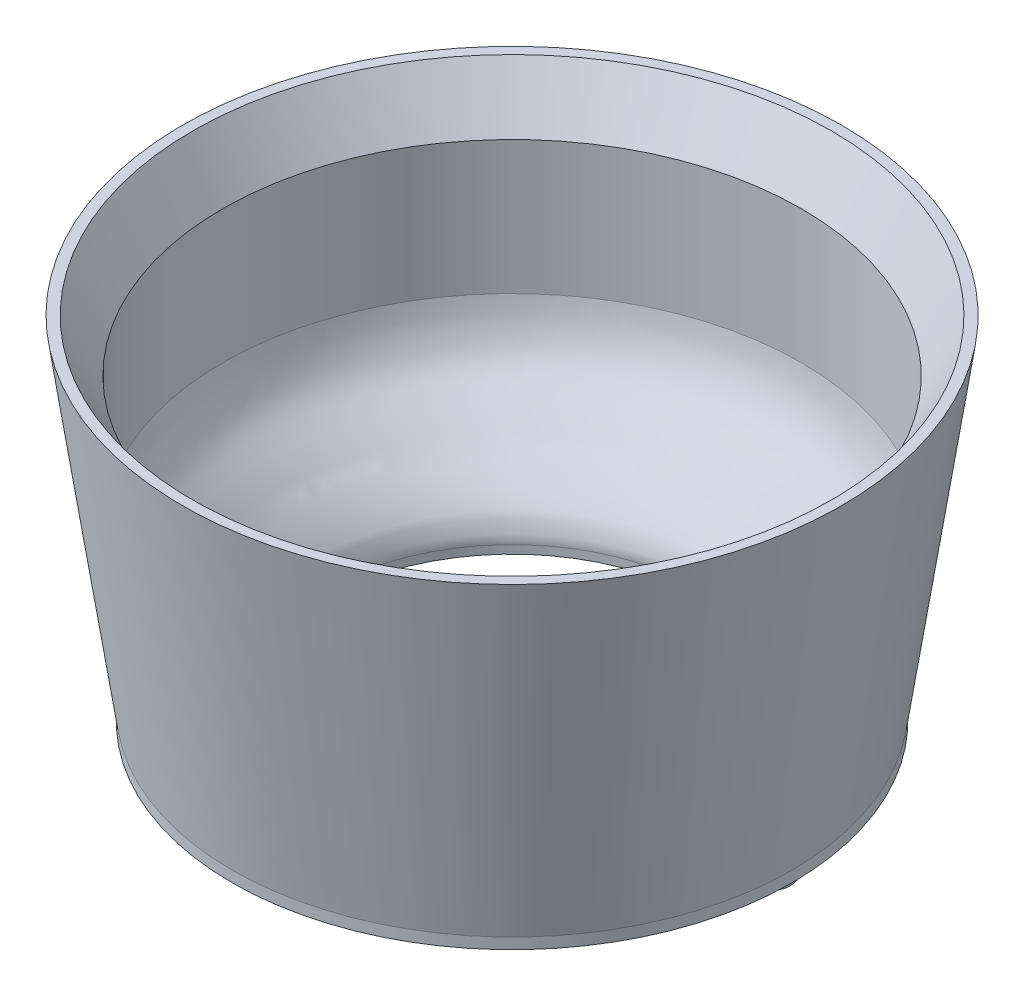
SolidWorks part; units mm, degrees
material "ABS PC"
ref_plane "Front Plane" through (0, 0, 0) normal (0, 0, 1) x (1, 0, 0)
ref_plane "Top Plane" through (0, 0, 0) normal (0, 1, 0) x (1, 0, 0)
ref_plane "Right Plane" through (0, 0, 0) normal (1, 0, 0) x (0, 0, -1)
sketch "Sketch1" plane through (0, 0, 0) normal (1, 0, 0) x (0, 0, -1)
  line L0 (26.0878, 274.978) -> (26.0878, 232.1195)
  line L2 (40.135, 299.274) -> (-40.135, 299.274) construction
  line L5 (0, 324) -> (3.2968, 324)
  line L8 (0, 324) -> (0, 0) construction
  line L9 (26.0878, 262.3641) -> (26.0878, 259.4973) construction
  line L12 (40.135, 302.9291) -> (40.135, 295.6188)
  line L16 (0, 0) -> (51.9362, 327.9125) construction
  line L17 (0, 324) -> (0, 332) construction
  line L18 (26.0878, 274.978) -> (26.0878, 268.978) construction
  line L19 (26.0878, 268.978) -> (26.0878, 248.978) construction
  line L20 (26.0878, 268.978) -> (42.6019, 268.978) construction
  line L21 (26.0878, 274.978) -> (43.5522, 274.978) construction
  line L22 (26.0878, 248.978) -> (39.4342, 248.978) construction
  line L23 (0, 0) -> (-51.9362, 327.9125) construction
  line L24 (-47.4003, 299.274) -> (-47.4003, 268.978) construction
  line L25 (-47.4003, 268.978) -> (-42.6019, 268.978) construction
  line L26 (0, 332) -> (0, 76.96) construction
  line L27 (0, 76.96) -> (400, 76.96) construction
  line L28 (0, 76.96) -> (-400, 76.96) construction
  line L29 (-200, 76.96) -> (-200, 183.96) construction
  line L30 (200, 76.96) -> (200, 183.96) construction
  line L31 (-200, 183.96) -> (-200, 182.57) construction
  line L32 (-200, 182.57) -> (400, 182.57) construction
  line L33 (-200, 182.57) -> (-400, 182.57) construction
  line L38 (0, 186.1152) -> (0, 324)
  line L39 (26.0878, 232.1195) -> (26.0878, 182.57) construction
  line L41 (21.6442, 226.0993) -> (26.0878, 226.0993)
  line L42 (26.0878, 226.0993) -> (26.0878, 186.1152)
  line L43 (26.0878, 186.1152) -> (0, 186.1152)
  line L44 (0, 0) -> (575.122, 0) construction
  arc A0 (-298.7691, 144.7791) -> (305.6579, 129.6043) centre (0, 0) cw construction
  spline S0 degree 3 poles (21.6442, 226.0993) (21.9584, 226.1509) (22.4049, 226.153) (22.896, 226.3321) (23.44, 226.7494) (24.2443, 227.2014) (25.0066, 227.9724) (25.5796, 228.9522) (25.8622, 230.393) (26.0228, 231.4436) (26.0878, 232.1195) knots 0 0 0 0 0.091924 0.112491 0.205673 0.333714 0.459267 0.602423 0.748839 1 1 1 1
  spline S1 degree 3 poles (3.2968, 324) (4.1972, 323.8396) (5.699, 323.816) (7.6935, 323.4297) (9.2722, 323.1563) (10.7507, 322.8538) (12.1816, 322.5577) (13.6372, 322.313) (14.8643, 321.9117) (15.9115, 321.5662) (16.81, 321.2491) (17.7339, 321.0149) (18.8379, 320.6416) (19.931, 320.1935) (21.0686, 319.6948) (22.141, 319.2627) (23.2156, 318.6856) (24.4371, 318.1163) (25.6762, 317.3518) (27.1066, 316.7518) (28.4318, 315.7832) (29.7322, 314.8939) (31.058, 313.93) (32.1959, 312.8581) (33.3378, 311.8503) (34.4539, 310.9646) (35.3895, 309.8867) (36.5078, 309.0949) (37.2942, 308.0208) (38.1233, 307.1238) (38.9048, 306.0961) (39.4724, 304.6349) (40.2774, 303.734) (40.135, 302.9291) knots 0 0 0 0 0.061585 0.100795 0.136831 0.1697 0.202569 0.235438 0.269088 0.289473 0.309858 0.333319 0.353706 0.388423 0.412965 0.437514 0.46634 0.495168 0.528354 0.564387 0.59925 0.638593 0.670824 0.709635 0.743897 0.773612 0.805519 0.839783 0.864953 0.89467 0.922395 0.951224 1 1 1 1
  spline S2 degree 3 poles (40.135, 295.6188) (39.9636, 294.7131) (39.7869, 293.3689) (39.1095, 291.6901) (38.6019, 290.4599) (37.8418, 289.2392) (36.9195, 288.2279) (35.9232, 287.2651) (34.974, 286.2515) (33.8311, 285.3463) (32.8233, 284.2966) (31.8701, 283.2868) (30.7668, 282.4387) (29.8742, 281.4644) (28.8604, 280.5152) (28.0567, 279.5119) (27.1438, 278.5569) (26.4968, 277.0287) (26.0081, 275.8567) (26.0878, 274.978) knots 0 0 0 0 0.108356 0.15601 0.210945 0.263562 0.322855 0.370186 0.4254 0.484692 0.539909 0.595126 0.646549 0.701764 0.749093 0.808384 0.85195 0.901837 1 1 1 1
  point P10 (0, 299.274)
  point P63 (0, 299.274)
  dimension "D3" = 9
  dimension "D1" = 40.135
  dimension "D2" = 324
  dimension "D4" = 8
  dimension "D5" = 3.2968
  dimension "D6" = 4.4435
  dimension "D7" = 6.0202
  dimension "D8" = 7.7403
  dimension "D9" = 6
  dimension "D10" = 20
  dimension "D11" = 9.317
  dimension "D12" = 10.7504
  dimension "D13" = 255.04
  dimension "D14" = 107
  dimension "D15" = 107
  dimension "D16" = 332
  dimension "D17" = 105.61
  dimension "D18" = 105.61
  dimension "D19" = 12.1838
  dimension "D20" = 13.6172
  dimension "D21" = 15.0506
  dimension "D22" = 15.9106
  dimension "D23" = 16.7707
  dimension "D24" = 17.7739
  dimension "D25" = 18.6341
  dimension "D26" = 20.0676
  dimension "D27" = 21.0708
  dimension "D28" = 22.0743
  dimension "D29" = 23.2209
  dimension "D30" = 24.3677
  dimension "D31" = 25.6578
  dimension "D32" = 27.0911
  dimension "D33" = 28.3811
  dimension "D34" = 29.8146
  dimension "D35" = 30.9613
  dimension "D36" = 32.2513
  dimension "D37" = 33.3981
  dimension "D38" = 34.4014
  dimension "D39" = 35.4048
  dimension "D40" = 36.5516
  dimension "D41" = 37.2681
  dimension "D42" = 38.1282
  dimension "D43" = 38.8449
  dimension "D44" = 39.4183
  dimension "D45" = 39.9917
  dimension "D46" = 323.8567
  dimension "D47" = 323.7133
  dimension "D48" = 323.4267
  dimension "D49" = 323.1399
  dimension "D50" = 322.8533
  dimension "D51" = 322.5666
  dimension "D52" = 322.2799
  dimension "D53" = 321.8499
  dimension "D54" = 321.5632
  dimension "D55" = 321.2765
  dimension "D56" = 320.9899
  dimension "D57" = 320.7031
  dimension "D58" = 320.1297
  dimension "D59" = 319.6998
  dimension "D60" = 319.2698
  dimension "D61" = 318.6965
  dimension "D62" = 318.1231
  dimension "D63" = 317.4064
  dimension "D64" = 316.6897
  dimension "D65" = 315.8296
  dimension "D66" = 314.8263
  dimension "D67" = 313.9663
  dimension "D68" = 312.8195
  dimension "D69" = 311.8162
  dimension "D70" = 310.9562
  dimension "D71" = 309.9528
  dimension "D72" = 308.9493
  dimension "D73" = 308.0893
  dimension "D74" = 307.086
  dimension "D75" = 306.0826
  dimension "D76" = 304.9359
  dimension "D77" = 303.9325
  dimension "D78" = 302.9291
sketch "Sketch2" plane through (0, 0, 0) normal (1, 0, 0) x (0, 0, -1)
  line L0 (0, 324) -> (3.2968, 324) construction
  line L1 (26.5078, 274.997) -> (26.5078, 273.8486)
  line L2 (40.5477, 295.5407) -> (40.5477, 314.2386)
  line L3 (40.135, 295.6188) -> (40.135, 302.9302) construction
  line L4 (40.135, 295.6188) -> (26.0878, 274.978) construction
  line L5 (0, 324.42) -> (3.4084, 324.42) construction
  line L6 (3.2968, 324) -> (40.135, 302.9302) construction
  line L7 (3.4084, 324.42) -> (40.555, 303.1738) construction
  line L8 (26.0878, 274.978) -> (26.0878, 232.1195) construction
  line L9 (40.555, 295.4895) -> (26.435, 274.7417) construction
  line L10 (0, 5) -> (0, 407.9498) construction
  line L12 (26.5078, 273.8486) -> (38.5078, 273.8486) construction
  line L13 (26.5078, 274.997) -> (26.5078, 232.1195) construction
  line L14 (38.5078, 273.8486) -> (45.76, 323.5611) construction
  line L17 (40.5477, 314.2386) -> (45.93, 323.5611) construction
  line L18 (45.93, 323.5611) -> (45.76, 323.5611) construction
  line L19 (0, 186.1152) -> (0, 324) construction
  line L20 (0, 324) -> (0, 332) construction
  line L21 (40.555, 295.4895) -> (40.555, 303.1738) construction
  line L22 (0, 5) -> (47.1644, 328.2999) construction
  line L23 (45.93, 323.5611) -> (46.473, 323.5611) construction
  line L24 (46.473, 323.5611) -> (39.2208, 273.8486) construction
  line L25 (39.2208, 273.8486) -> (26.5078, 273.8486)
  line L26 (44.7753, 321.5611) -> (46.1813, 321.5611)
  line L27 (44.7753, 321.5611) -> (40.5477, 314.2386)
  line L28 (46.1813, 321.5611) -> (39.2208, 273.8486)
  spline S0 degree 1 poles (40.5477, 295.5407) (26.5078, 274.997) knots 0 0 1 1 construction
  spline S1 degree 3 poles (40.135, 295.6188) (39.9636, 294.7131) (39.7869, 293.3689) (39.1095, 291.6901) (38.6019, 290.4599) (37.8418, 289.2392) (36.9195, 288.2279) (35.9232, 287.2651) (34.974, 286.2515) (33.8311, 285.3463) (32.8233, 284.2966) (31.8701, 283.2868) (30.7668, 282.4387) (29.8742, 281.4644) (28.8604, 280.5152) (28.0567, 279.5119) (27.1438, 278.5569) (26.4968, 277.0287) (26.0081, 275.8567) (26.0878, 274.978) knots 0 0 0 0 0.108356 0.15601 0.210945 0.263562 0.322855 0.370186 0.4254 0.484692 0.539909 0.595126 0.646549 0.701764 0.749093 0.808384 0.85195 0.901837 1 1 1 1 construction
  spline S2 degree 3 poles (40.5477, 295.5407) (40.4477, 295.0127) (40.2928, 293.9708) (39.9309, 292.5875) (39.5162, 291.5815) (39.1084, 290.578) (38.4397, 289.317) (37.3314, 288.0326) (36.3684, 287.1154) (35.6302, 286.3401) (35.0165, 285.7627) (34.3943, 285.2472) (33.6355, 284.5566) (32.9204, 283.7714) (32.1297, 282.9861) (31.4852, 282.4595) (30.915, 281.9635) (30.3717, 281.3913) (29.7828, 280.8046) (29.2276, 280.2622) (28.7248, 279.6749) (28.1804, 279.0397) (27.6518, 278.4702) (27.3081, 277.8768) (26.9952, 277.1272) (26.598, 276.1645) (26.4648, 275.4705) (26.5078, 274.997) knots 0 0 0 0 0.062544 0.125088 0.15636 0.187632 0.250176 0.31272 0.375264 0.406536 0.437808 0.46908 0.500352 0.562896 0.594168 0.62544 0.656713 0.687985 0.719257 0.750529 0.781801 0.813073 0.844345 0.875617 0.906889 0.938161 1.000705 1.000705 1.000705 1.000705
  point P38 (0, 328)
  dimension "D4" = 1.1484
  dimension "D5" = 8.3
  dimension "D6" = 30
  dimension "D7" = 45.93
  dimension "D8" = 40.39
  dimension "D9" = 8.3
  dimension "D10" = 40.5477
  dimension "D3" = 12
  dimension "D11" = 18.6979
  dimension "D12" = 2
  dimension "D13" = 5
  dimension "D1" = 0.42
  dimension "D2" = 0.42
revolve "Revolve6" add sketch "Sketch2" angle 360 about L10
sketch "Sketch3" plane through (0, 0, 0) normal (1, 0, 0) x (0, 0, -1)
  line L0 (44.1979, 321.5611) -> (40.5477, 314.2386) construction
  line L3 (46.1813, 321.5611) -> (-46.1813, 321.5611) construction
  line L4 (44.7753, 321.5611) -> (-44.7753, 321.5611) construction
  line L5 (40.5477, 314.2386) -> (-40.5477, 314.2386) construction
  line L6 (40.5477, 314.2386) -> (54.812, 333.8718)
  line L8 (54.812, 333.8718) -> (54.812, 347.837)
  line L9 (54.812, 347.837) -> (0, 347.837)
  line L10 (0, 347.837) -> (0, 311.6751)
  line L11 (0, 186.1152) -> (0, 324) construction
  line L12 (0, 311.6751) -> (40.5477, 311.6751)
  line L13 (40.5477, 311.6751) -> (40.5477, 314.2386)
  dimension "D1" = 36
  dimension "D2" = 54.812
revolve "Cut-Revolve1" [suppressed] cut sketch "Sketch3" angle 360 about L10
sketch "Sketch4" plane through (0, 273.8486, 0) normal (0, -1, 0) x (1, 0, 0)
  line L0 (0, 0) -> (36, 0) construction
  line L1 (0, 0) -> (-31.1769, 18) construction
  circle A0 centre (0, 0) radius 36 construction
  circle A1 centre (-31.1769, 18) radius 3
  circle A2 centre (36, 0) radius 3
  dimension "D1" = 72
  dimension "D3" = 6
  dimension "D4" = 6
  dimension "D2" = 150
extrude "Boss-Extrude1" add sketch "Sketch4" along normal blind 2
sketch "Sketch5" [suppressed] plane through (0, 263.8486, 0) normal (0, -1, 0) x (1, 0, 0)
  circle A0 centre (36, 0) radius 3.175
  circle A1 centre (-31.1769, 18) radius 3.175
  dimension "D1" = 6.35
  dimension "D2" = 6.35
extrude "Boss-Extrude2" [suppressed] add sketch "Sketch5" along normal blind 5
chamfer "Chamfer2" [suppressed] distance 9 angle 4
sketch "Sketch7" plane through (0, 0, 0) normal (1, 0, 0) x (0, 0, -1)
  line L0 (0, 5) -> (0, 407.9498) construction
  line L1 (26.5078, 273.8486) -> (39.2208, 273.8486) construction
  line L2 (39.2208, 273.8486) -> (39.2208, 272.3194)
  line L4 (26.5078, 273.8486) -> (26.5078, 274.3486)
  line L5 (26.5078, 274.3486) -> (39.2208, 274.3486)
  line L6 (39.2208, 274.3486) -> (39.2208, 273.8486)
  circle A0 centre (0, -0.122) radius 275.25 construction
  arc A1 (39.2208, 272.3194) -> (26.5078, 273.8486) centre (0, -0.122) ccw
  dimension "D1" = 550.5
  dimension "D2" = 0.5
revolve "Revolve7" add sketch "Sketch7" angle 360 about L10
sketch "Sketch9" plane through (0, 271.8486, 0) normal (0, -1, 0) x (1, 0, 0)
  circle A0 centre (36, 0) radius 1.5
  circle A1 centre (-31.1769, 18) radius 1.5
  dimension "D1" = 3
  dimension "D2" = 3
extrude "Cut-Extrude1" cut sketch "Sketch9" against normal blind 6
sketch "Sketch10" plane through (0, 271.8486, 0) normal (0, -1, 0) x (1, 0, 0)
  circle A0 centre (36, 0) radius 2
  circle A1 centre (-31.1769, 18) radius 2
  dimension "D1" = 4
  dimension "D2" = 4
extrude "Cut-Extrude2" cut sketch "Sketch10" against normal blind 0.5
chamfer "Chamfer3" distance 0.55 angle 45 2 edges at (36, 271.8486, -2) (-31.1769, 271.8486, 16)
